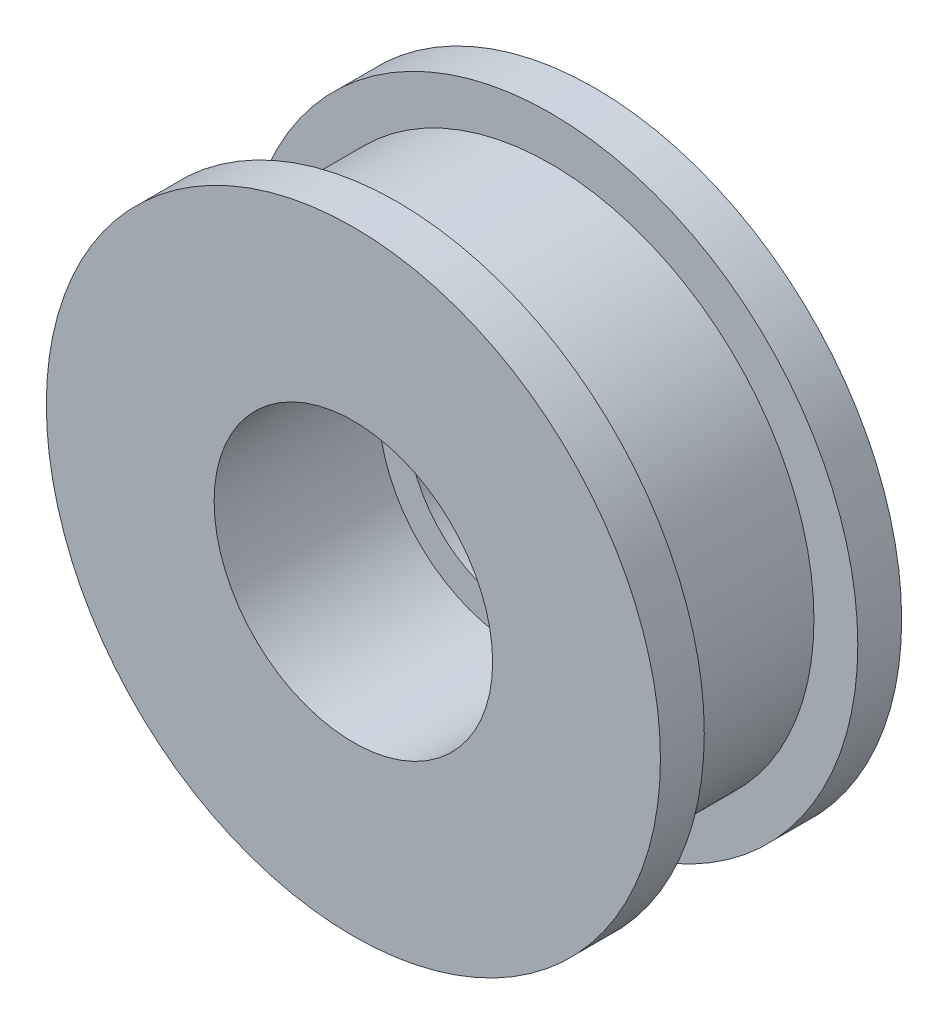
SolidWorks part; units mm, degrees
material "6061 Alloy"
ref_plane "Front Plane" through (0, 0, 0) normal (0, 0, 1) x (1, 0, 0)
ref_plane "Top Plane" through (0, 0, 0) normal (0, 1, 0) x (1, 0, 0)
ref_plane "Right Plane" through (0, 0, 0) normal (1, 0, 0) x (0, 0, -1)
sketch "Sketch1" plane through (0, 0, 0) normal (0, 0, 1) x (1, 0, 0)
  circle A0 centre (0, 0) radius 14
  circle A1 centre (0, 0) radius 12
  circle A2 centre (0, 0) radius 2
  dimension "D1" = 28
  dimension "D2" = 24
  dimension "D3" = 4
extrude "Top Flange" add sketch "Sketch1" along normal blind 2 contours A0 A1 | A1 A2 region at (-13.604, 0, 0) region at (-11.6606, 0, 0)
extrude "Center Spindle" add sketch "Sketch1<3>" along normal blind 9 contours A1 A2 region at (-11.6606, 0, 0)
sketch "Sketch1<3>" plane through (0, 0, 0) normal (0, 0, 1) x (1, 0, 0) same geometry as "Sketch1"
extrude "Bottom Flange" add sketch "Sketch1<4>" along normal blind 2 from offset 9 contours A0 A1 | A1 A2 region at (-13.604, 0, 0) region at (-11.6606, 0, 0)
sketch "Sketch1<4>" plane through (0, 0, 0) normal (0, 0, 1) x (1, 0, 0) same geometry as "Sketch1"
sketch "Sketch2" plane through (0, 0, 11) normal (0, 0, 1) x (1, 0, 0)
  circle A0 centre (0, 0) radius 6.35
  circle A1 centre (0, 0) radius 5
  circle M2 centre (0, 0) radius 2
extrude "Bearing Recess" cut sketch "Sketch2" against normal blind 7.5 contours A1 M2 | A0 A1 region at (-6.1704, 0, 11) region at (-4.8586, 0, 11)
extrude "Screw Opening" cut sketch "Sketch2<3>" against normal through all contours A1 M2 region at (-4.8586, 0, 11)
sketch "Sketch2<3>" plane through (0, 0, 11) normal (0, 0, 1) x (1, 0, 0) same geometry as "Sketch2"
